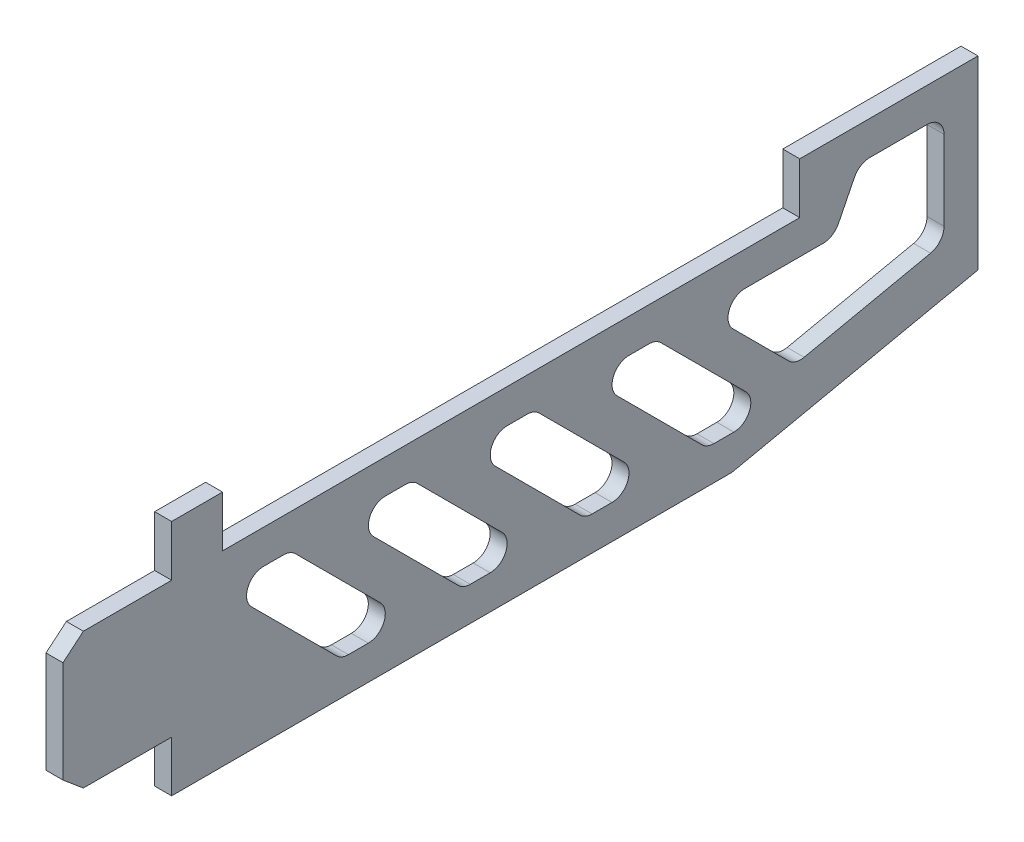
SolidWorks part; units mm, degrees
ref_plane "Ebene vorne" through (0, 0, 0) normal (0, 0, 1) x (1, 0, 0)
ref_plane "Ebene oben" through (0, 0, 0) normal (0, 1, 0) x (1, 0, 0)
ref_plane "Ebene rechts" through (0, 0, 0) normal (1, 0, 0) x (0, 0, -1)
sketch "Skizze1" plane through (0, 0, 0) normal (1, 0, 0) x (0, 0, -1)
  line L1 (0, 0) -> (237.5, 0)
  line L2 (0, 0) -> (0, 70)
  line L3 (0, 70) -> (237.5, 70)
  line L4 (237.5, 0) -> (237.5, 70)
  dimension "D1" = 70
  dimension "D2" = 237.5
extrude "Aufsatz-Linear austragen1" add sketch "Skizze1" along normal blind 5
sketch "Skizze2" plane through (5, 0, 0) normal (1, 0, 0) x (0, 0, -1)
  line L0 (165, 0) -> (237.5, 15.4104)
  line L1 (0, 0) -> (237.5, 0) construction
  line L2 (237.5, 0) -> (237.5, 70) construction
  line L3 (237.5, 15.4104) -> (237.5, 0)
  line L4 (237.5, 0) -> (165, 0)
  dimension "D1" = 12
  dimension "D2" = 165
extrude "Schnitt-Linear austragen1" cut sketch "Skizze2" against normal through all
sketch "Skizze3" plane through (5, 0, 0) normal (1, 0, 0) x (0, 0, -1)
  line L0 (237.5, 70) -> (0, 70) construction
  line L1 (15, 70) -> (185, 70)
  line L2 (15, 70) -> (15, 55)
  line L3 (15, 55) -> (185, 55)
  line L4 (185, 70) -> (185, 55)
  line L5 (0, 70) -> (0, 0) construction
  dimension "D1" = 170
  dimension "D2" = 15
  dimension "D3" = 15
extrude "Schnitt-Linear austragen2" cut sketch "Skizze3" against normal blind 5
sketch "Skizze4" plane through (5, 0, 0) normal (1, 0, 0) x (0, 0, -1)
  line L0 (15, 55) -> (15, 27.5) construction
  line L1 (15, 27.5) -> (15, 0) construction
  line L2 (0, 0) -> (165, 0) construction
  line L3 (15, 27.5) -> (237.5, 27.5) construction
  line L4 (237.5, 15.4104) -> (237.5, 70) construction
  line L5 (15, 45) -> (50, 10)
  line L6 (15, 45) -> (35, 45)
  line L7 (50, 10) -> (70, 10)
  line L8 (35, 45) -> (70, 10)
  line L9 (15, 55) -> (185, 55) construction
  line L10 (50.8845, 27.5) -> (273.3845, 27.5) construction
  line L11 (50.8845, 45) -> (70.8845, 45)
  line L12 (70.8845, 45) -> (105.8845, 10)
  line L13 (85.8845, 10) -> (105.8845, 10)
  line L14 (50.8845, 45) -> (85.8845, 10)
  line L15 (86.769, 27.5) -> (309.269, 27.5) construction
  line L16 (86.769, 45) -> (106.769, 45)
  line L17 (106.769, 45) -> (141.769, 10)
  line L18 (121.769, 10) -> (141.769, 10)
  line L19 (86.769, 45) -> (121.769, 10)
  line L20 (122.6535, 27.5) -> (345.1535, 27.5) construction
  line L21 (122.6535, 45) -> (142.6535, 45)
  line L22 (142.6535, 45) -> (177.6535, 10)
  line L23 (157.6535, 10) -> (177.6535, 10)
  line L24 (122.6535, 45) -> (157.6535, 10)
  line L25 (227.5, 60) -> (227.5, 27.5)
  line L26 (227.5, 27.5) -> (183.6222, 18.1735)
  line L27 (183.6222, 18.1735) -> (156.7957, 45)
  line L28 (156.7957, 45) -> (195, 45)
  line L29 (195, 45) -> (202.5, 60)
  line L30 (202.5, 60) -> (227.5, 60)
  line L32 (237.5, 15.4104) -> (165, 0) construction
  line L33 (237.5, 70) -> (185, 70) construction
  line L34 (185, 55) -> (185, 70) construction
  point P3 (32.5, 27.5)
  dimension "D1" = 10
  dimension "D2" = 45
  dimension "D3" = 20
  dimension "D5" = 10
  dimension "D6" = 10
  dimension "D7" = 10
  dimension "D8" = 10
  dimension "D9" = 25
  dimension "D10" = 10
  dimension "D4" = 4
extrude "Schnitt-Linear austragen3" cut sketch "Skizze4" against normal through all
fillet "Verrundung1" radius 5 22 edges at (2.5, 10, -157.6535) (2.5, 10, -177.6535) (2.5, 45, -142.6535) (2.5, 45, -122.6535) (2.5, 45, -86.769) (2.5, 45, -106.769) (2.5, 10, -141.769) (2.5, 10, -121.769) (2.5, 10, -85.8845) (2.5, 10, -105.8845) (2.5, 45, -70.8845) (2.5, 45, -50.8845) (2.5, 10, -50) (2.5, 10, -70) (2.5, 45, -35) (2.5, 45, -15) (2.5, 18.1735, -183.6222) (2.5, 27.5, -227.5) (2.5, 60, -227.5) (2.5, 45, -195) (2.5, 60, -202.5) (2.5, 45, -156.7957)
sketch "Skizze5" plane through (5, 0, 0) normal (1, 0, 0) x (0, 0, -1)
  line L0 (0, 55) -> (-26, 55)
  line L1 (0, 70) -> (0, 0) construction
  line L2 (-26, 55) -> (-32, 49.9654)
  line L3 (-32, 49.9654) -> (-32, 20.0346)
  line L4 (-32, 35) -> (0, 35) construction
  line L5 (0, 55) -> (0, 15)
  line L6 (-26, 15) -> (-32, 20.0346)
  line L7 (0, 15) -> (-26, 15)
  point P10 (0, 40.104)
  point P11 (0, 27.6198)
  point P12 (0, 35)
  dimension "D1" = 32
  dimension "D2" = 40
  dimension "D3" = 140
  dimension "D4" = 26
extrude "LascheNase" add sketch "Skizze5" against normal up to surface (5 mm away) up to face at (0, 42.0364, -199.758)
